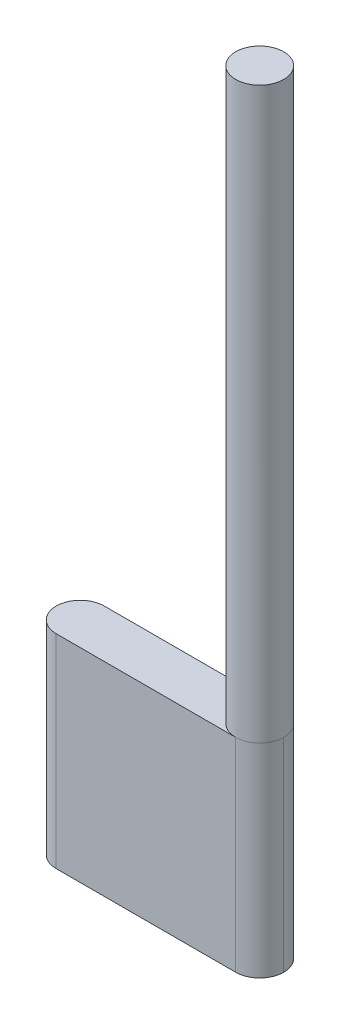
SolidWorks part; units mm, degrees
ref_plane "Front Plane" through (0, 0, 0) normal (0, 0, 1) x (1, 0, 0)
ref_plane "Top Plane" through (0, 0, 0) normal (0, 1, 0) x (1, 0, 0)
ref_plane "Right Plane" through (0, 0, 0) normal (1, 0, 0) x (0, 0, -1)
sketch "Sketch1" plane through (0, 0, 0) normal (0, 1, 0) x (1, 0, 0)
  circle A0 centre (0, 0) radius 2.95
  dimension "D1" = 5.9
extrude "Boss-Extrude1" add sketch "Sketch1" along normal mid plane 70
sketch "Sketch2" plane through (0, -35, 0) normal (0, -1, 0) x (1, 0, 0)
  line L0 (-2.95, 2.95) -> (-25, 2.95)
  line L1 (-2.95, 2.95) -> (2.95, 2.95)
  line L3 (-2.95, -2.95) -> (2.95, -2.95)
  line L4 (2.95, 2.95) -> (2.95, -2.95)
  line L5 (-2.95, 2.95) -> (2.95, -2.95) construction
  line L6 (-2.95, -2.95) -> (2.95, 2.95) construction
  line L7 (-25, 2.95) -> (-25, -2.95)
  line L8 (-25, -2.95) -> (-2.95, -2.95)
  point P0 (0, 0)
  dimension "D1" = 5.9
  dimension "D2" = 5.9
  dimension "D3" = 25
extrude "Boss-Extrude2" add sketch "Sketch2" along normal blind 25
fillet "Fillet1" radius 2.95 4 edges at (-25, -47.5, 2.95) (-25, -47.5, -2.95) (2.95, -47.5, -2.95) (2.95, -47.5, 2.95)
